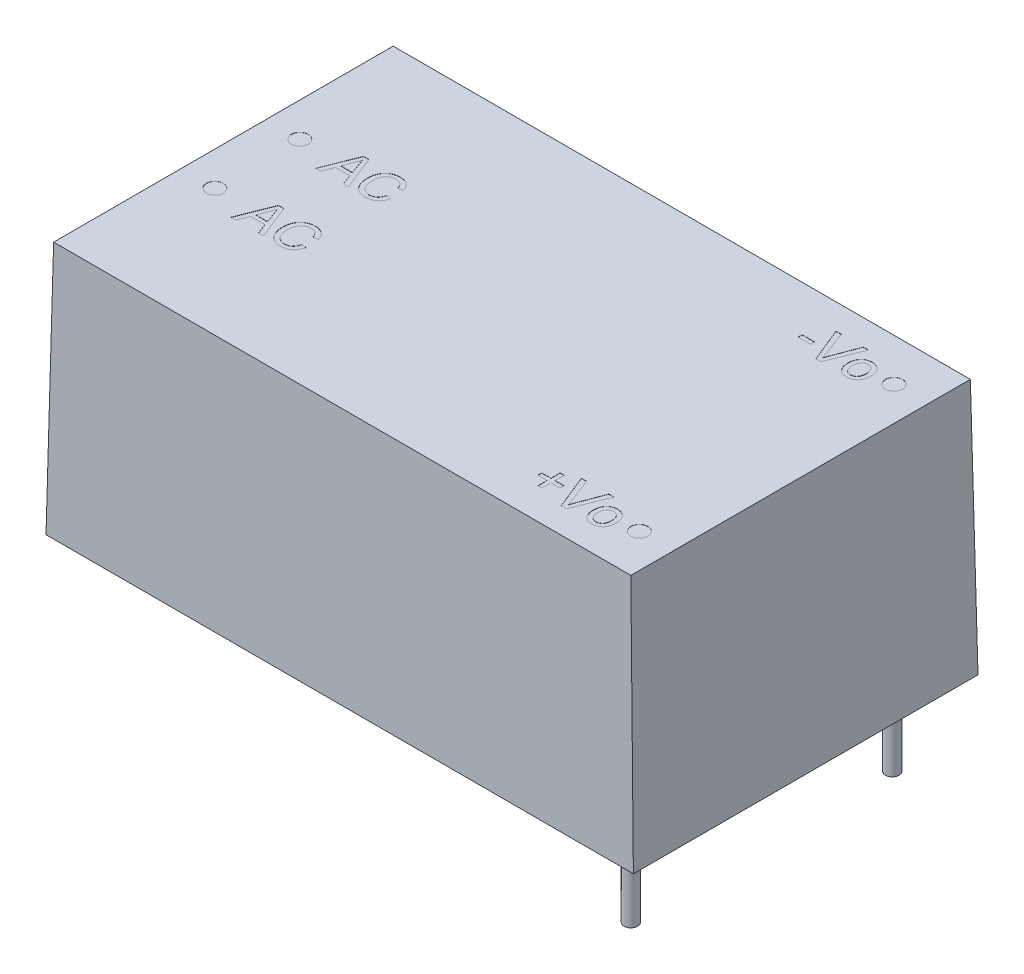
SolidWorks part; units mm, degrees
ref_plane "Спереди" through (0, 0, 0) normal (0, 0, 1) x (1, 0, 0)
ref_plane "Сверху" through (0, 0, 0) normal (0, 1, 0) x (1, 0, 0)
ref_plane "Справа" through (0, 0, 0) normal (1, 0, 0) x (0, 0, -1)
sketch "Эскиз1" plane through (0, 0, 0) normal (0, 1, 0) x (1, 0, 0)
  line L1 (-17.3, 10.15) -> (17.3, 10.15)
  line L2 (-17.3, 10.15) -> (-17.3, -10.15)
  line L3 (-17.3, -10.15) -> (17.3, -10.15)
  line L4 (17.3, 10.15) -> (17.3, -10.15)
  point P4 (0, 10.15)
  point P6 (-17.3, 0)
  dimension "D1" = 34.6
  dimension "D2" = 20.3
ref_plane "Плоскость1" through (0, 15, 0) normal (0, 1, 0) x (1, 0, 0)
sketch "Эскиз2" plane through (0, 15, 0) normal (0, 1, 0) x (1, 0, 0)
  line L1 (-17, 10) -> (17, 10)
  line L2 (-17, 10) -> (-17, -10)
  line L3 (-17, -10) -> (17, -10)
  line L4 (17, 10) -> (17, -10)
  point P4 (0, 10)
  point P6 (-17, 0)
  dimension "D1" = 34
  dimension "D2" = 20
loft "По сечениям1" add profiles "Эскиз1", "Эскиз2" connector at (17.3, 0, -10.15) connector at (17, 15, -10)
sketch "Эскиз3" plane through (0, 0, 0) normal (0, -1, 0) x (1, 0, 0)
  line L0 (-14.7, 2.5) -> (-14.7, -2.5) construction
  line L1 (14.7, 7.7) -> (14.7, -7.7) construction
  line L2 (-14.7, 0) -> (14.7, 0) construction
  circle A0 centre (-14.7, 2.5) radius 0.4
  circle A1 centre (-14.7, -2.5) radius 0.4
  circle A2 centre (14.7, 7.7) radius 0.4
  circle A3 centre (14.7, -7.7) radius 0.4
  point P8 (14.7, 0)
  point P9 (-14.7, 0)
  point P13 (0, 0)
  dimension "D4" = 0.8
  dimension "D1" = 5
  dimension "D2" = 15.4
  dimension "D3" = 29.4
extrude "Бобышка-Вытянуть1" add sketch "Эскиз3" along normal blind 5 separate body
sketch "Эскиз4" plane through (0, 15, 0) normal (0, 1, 0) x (1, 0, 0)
  line L0 (-15, 2.5) -> (-15, -2.5) construction
  line L1 (15, 7.5) -> (15, -7.5) construction
  line L2 (-15, 0) -> (15, 0) construction
  line L3 (17, 10) -> (17, -10) construction
  line L4 (-15, 2.5) -> (15, 2.5) construction
  line L5 (-15, -2.5) -> (15, -2.5) construction
  line L6 (15, 7.5) -> (-15, 7.5) construction
  line L7 (15, -7.5) -> (-15, -7.5) construction
  line L8 (-13, 1.5) -> (15, 1.5) construction
  line L9 (-13, -3.5) -> (15, -3.5) construction
  line L10 (14, 6.5) -> (-15, 6.5) construction
  line L11 (14, -8.5) -> (-15, -8.5) construction
  circle A0 centre (-15, 2.5) radius 0.5
  circle A1 centre (-15, -2.5) radius 0.5
  circle A2 centre (15, 7.5) radius 0.5
  circle A3 centre (15, -7.5) radius 0.5
  text T0 "AC" font "Arial" height 2
  text T1 "AC" font "Arial" height 2
  text T2 "-Vo" font "Arial" height 2
  text T3 "+Vo" font "Arial" height 2
  point P27 (13.6986, -8.5)
  dimension "D1" = 1
  dimension "D2" = 15
  dimension "D3" = 2
  dimension "D4" = 5
  dimension "D5" = 1
  dimension "D6" = 2
  dimension "D7" = 1
  dimension "D8" = 1
  dimension "D9" = 1
  dimension "D10" = 2
extrude "Вырез-Вытянуть1" cut sketch "Эскиз4" against normal blind 0.01
